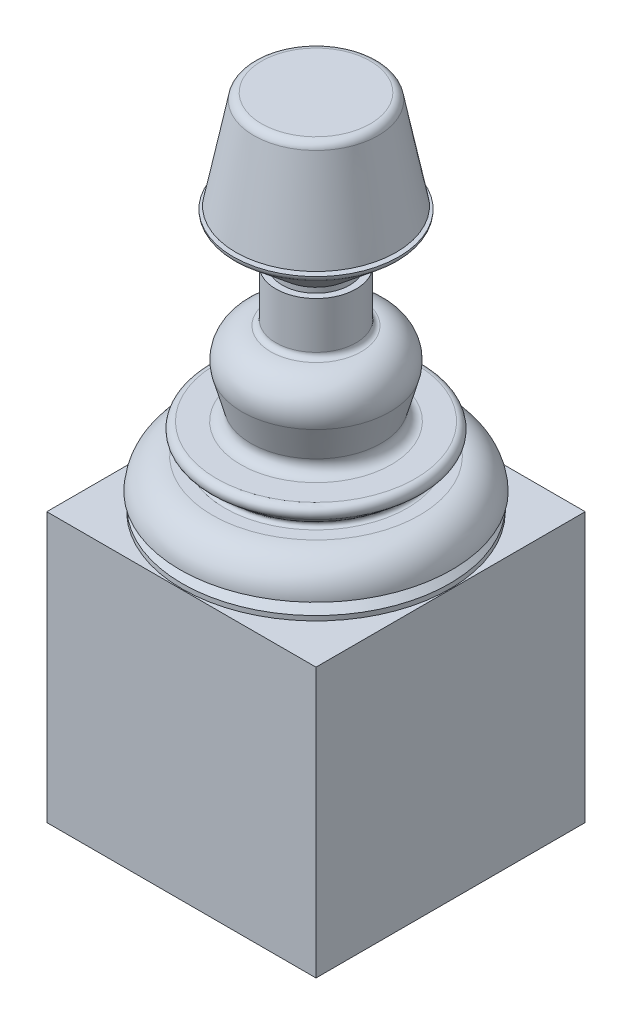
SolidWorks part; units mm, degrees
ref_plane "Płaszczyzna przednia" through (0, 0, 0) normal (0, 0, 1) x (1, 0, 0)
ref_plane "Płaszczyzna górna" through (0, 0, 0) normal (0, 1, 0) x (1, 0, 0)
ref_plane "Płaszczyzna prawa" through (0, 0, 0) normal (1, 0, 0) x (0, 0, -1)
sketch "Szkic1" plane through (0, 0, 0) normal (1, 0, 0) x (0, 0, -1)
  line L0 (0, 0) -> (25.85, 0)
  line L1 (20, 9.4) -> (17.6211, 9.4)
  line L2 (17.2243, 10.4989) -> (20.0306, 12.8295)
  line L3 (19.2, 15.1296) -> (14.5361, 15.1296)
  line L4 (12.5754, 17.7145) -> (14.2871, 23.8296)
  line L5 (7.75, 32.1296) -> (7.75, 41.1296)
  line L6 (7.75, 41.1296) -> (6.5, 41.1296)
  line L7 (6.5, 41.1296) -> (6.5, 42.1296)
  line L8 (6.5, 42.1296) -> (15.5306, 49.6296)
  line L9 (16, 50.6296) -> (13, 50.6296)
  line L10 (13, 50.6296) -> (13, 51.1296)
  line L11 (13, 51.1296) -> (15.5, 51.1296)
  line L12 (15.5, 51.1296) -> (12, 68.8963)
  line L14 (0, 70.1296) -> (0, 0)
  line L15 (0, 97.6094) -> (0, -32.6912) construction
  line L16 (25.85, 0.9) -> (23, 3.4)
  line L17 (25.25, 3.4) -> (26.25, 3.4)
  line L18 (25.85, 0.9) -> (25.85, 0)
  line L19 (0, 70.1296) -> (10.5, 70.1296)
  line L20 (23, 3.4) -> (15, 3.4)
  line L21 (15, 3.4) -> (15, 6.4)
  line L22 (15, 6.4) -> (22.25, 6.4)
  line L23 (25.25, 3.4) -> (26.25, 3.4)
  arc A1 (17.6211, 9.4) -> (17.2243, 10.4989) centre (17.6211, 10.0211) cw
  arc A2 (20.0306, 12.8295) -> (19.2, 15.1296) centre (19.2, 13.8296) ccw
  arc A3 (14.5361, 15.1296) -> (12.5754, 17.7145) centre (14.5361, 17.1657) cw
  arc A4 (14.2871, 23.8296) -> (8.75, 31.1296) centre (8.75, 25.3796) ccw
  arc A5 (8.75, 31.1296) -> (7.75, 32.1296) centre (8.75, 32.1296) cw
  arc A6 (15.5306, 49.6296) -> (16, 50.6296) centre (14.7001, 50.6296) ccw
  arc A8 (26.25, 3.4) -> (20, 9.4) centre (20, 3.1448) ccw
  arc A9 (10.5, 70.1296) -> (12, 68.8963) centre (10.5, 68.6008) cw
  arc A10 (22.25, 6.4) -> (25.25, 3.4) centre (22.25, 3.4) cw
  point P41 (0, 0)
  point P42 (21.744, 6.4)
  dimension "D2" = 25.85
  dimension "D7" = 20
  dimension "D9" = 20.5
  dimension "D10" = 12.5
  dimension "D11" = 14.5
  dimension "D17" = 10.5
  dimension "D29" = 1
  dimension "D31" = 1.3
  dimension "D32" = 3
  dimension "D34" = 3
  dimension "D35" = 9.4
  dimension "D3" = 23
  dimension "D4" = 0.9
  dimension "D5" = 3.4
  dimension "D6" = 26.25
  dimension "D8" = 17
  dimension "D12" = 7.75
  dimension "D13" = 6.5
  dimension "D14" = 16
  dimension "D15" = 15.5
  dimension "D16" = 12
  dimension "D18" = 70.1296
  dimension "D19" = 19
  dimension "D20" = 0.5
  dimension "D21" = 13
  dimension "D22" = 28
  dimension "D23" = 1
  dimension "D24" = 1
  dimension "D25" = 38
  dimension "D26" = 1
  dimension "D27" = 55
  dimension "D28" = 6
  dimension "D30" = 7.3
  dimension "D33" = 8
  dimension "D36" = 1
revolve "Obrót1" add sketch "Szkic1" angle 360 about L15 region at (0, 31.6202, -7.747)
sketch "Szkic2" plane through (0, 0, 0) normal (0, -1, 0) x (1, 0, 0)
  line L1 (-15.25, -15.25) -> (15.25, -15.25) construction
  line L2 (-15.25, -15.25) -> (-15.25, 15.25) construction
  line L3 (-15.25, 15.25) -> (15.25, 15.25) construction
  line L4 (15.25, -15.25) -> (15.25, 15.25) construction
  line L5 (-15.25, -15.25) -> (15.25, 15.25) construction
  line L6 (-15.25, 15.25) -> (15.25, -15.25) construction
  circle A0 centre (0, 0) radius 18.5
  circle A1 centre (-15.25, 15.25) radius 0.95
  circle A2 centre (15.25, 15.25) radius 0.95
  circle A3 centre (-15.25, -15.25) radius 0.95
  circle A4 centre (15.25, -15.25) radius 0.95
  dimension "D1" = 37
  dimension "D3" = 1.9
  dimension "D2" = 30.5
extrude "Wytnij-wyciągnięcie1" cut sketch "Szkic2" against normal up to surface (6.4 mm away) up to face at (0, 6.4, 22.25)
shell "Skorupa2" thickness 2.5 removed face at (0, 6.4, 0)
sketch "Szkic3" plane through (0, 0, 0) normal (0, -1, 0) x (1, 0, 0)
  line L0 (-23, 0) -> (23, 0) construction
  circle A0 centre (-22, 0) radius 1
  circle A1 centre (22, 0) radius 1
  dimension "D1" = 2
  dimension "D2" = 46
extrude "Dodanie-wyciągnięcie1" add sketch "Szkic3" along normal blind 2
sketch "Szkic4" plane through (0, 0, 0) normal (0, -1, 0) x (1, 0, 0)
  line L1 (-26, -26) -> (26, -26)
  line L2 (-26, -26) -> (-26, 26)
  line L3 (-26, 26) -> (26, 26)
  line L4 (26, -26) -> (26, 26)
  line L5 (-26, -26) -> (26, 26) construction
  line L6 (-26, 26) -> (26, -26) construction
  point P0 (0, 0)
  dimension "D1" = 52
extrude "Dodanie-wyciągnięcie2" add sketch "Szkic4" along normal blind 52
